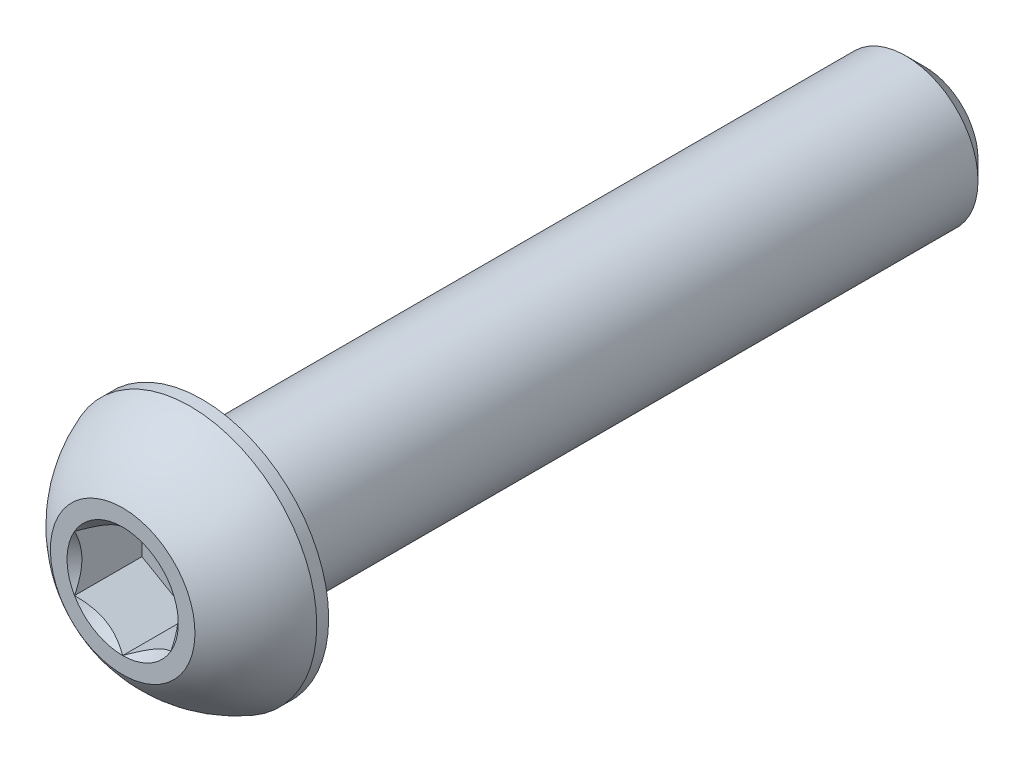
SolidWorks part; units mm, degrees
material "Alloy Steel"
ref_plane "Front Plane" through (0, 0, 0) normal (0, 0, 1) x (1, 0, 0)
ref_plane "Top Plane" through (0, 0, 0) normal (0, 1, 0) x (1, 0, 0)
ref_plane "Right Plane" through (0, 0, 0) normal (1, 0, 0) x (0, 0, -1)
sketch "Sketch1" plane through (0, 0, 0) normal (1, 0, 0) x (0, 0, -1)
  line L0 (-16.65, 0) -> (16.65, 0) construction
  line L1 (-13.35, 5.25) -> (-13.35, -5.25) construction
  line L2 (16.65, 3) -> (16.65, -3) construction
  line L3 (16.5875, 3.1083) -> (17.0875, 2.2422) construction
  line L4 (17.0875, 2.2422) -> (17.5875, 3.1083) construction
  line L5 (17.5875, 3.1083) -> (16.5875, 3.1083) construction
  line L6 (16.65, 3) -> (17.525, 3) construction
  line L7 (17.0875, 3.1083) -> (17.0875, 3) construction
  line L8 (17.0875, 3) -> (17.0875, 2.3505) construction
  line L9 (17.0875, 2.3505) -> (17.0875, 2.2422) construction
  line L10 (17.025, 2.3505) -> (17.15, 2.3505)
  line L11 (16.6188, 3.0541) -> (17.5563, 3.0541)
  line L12 (17.15, 2.3505) -> (17.5563, 3.0541)
  line L13 (17.025, 2.3505) -> (16.6188, 3.0541)
  line L14 (-16.65, 2) -> (-16.65, -2) construction
  line L15 (16.65, 3) -> (-13.35, 3) construction
  point P3 (-13.35, 0)
  point P6 (-13.85, 0)
  point P21 (17.0875, 3.0541)
  point P24 (-13.845, 5.25)
  point P25 (14.15, -3)
  point P26 (-16.65, 3)
  dimension "Head Height" = 3.3
  dimension "Length" = 30
  dimension "Head Dia" = 10.5
  dimension "Thread Dia" = 6
  dimension "Pitch" = 1
  dimension "D2" = 0.125
  dimension "Drive Size" = 4
  dimension "D1" = 2.8
  dimension "D3" = 0.495
  dimension "D4" = 2.5
sketch "Sketch2" plane through (0, 0, 0) normal (1, 0, 0) x (0, 0, -1)
  line L0 (-16.65, 0) -> (16.65, 0)
  line L1 (16.65, 0) -> (16.65, 2.2)
  line L2 (16.65, 3) -> (16.65, -3) construction
  line L3 (16.65, 2.2) -> (15.85, 3)
  line L4 (15.85, 3) -> (-13.35, 3)
  line L5 (-13.35, 5.25) -> (-13.35, -5.25) construction
  line L6 (-13.35, 3) -> (-13.35, 5.25)
  line L7 (-13.35, 5.25) -> (-13.845, 5.25)
  line L8 (16.65, 3) -> (17.525, 3) construction
  line L9 (-16.65, 0) -> (-16.65, 3)
  arc A0 (-16.65, 3) -> (-13.845, 5.25) centre (-11.9387, 0) cw
  dimension "D1" = 0.8
  dimension "D2" = 45
revolve "Revolve1" add sketch "Sketch2" angle 360 about L0
sketch "Sketch3" plane through (0, 0, 16.65) normal (0, 0, 1) x (1, 0, 0)
  line L1 (0, 2.3094) -> (-2, 1.1547)
  line L2 (-2, 1.1547) -> (-2, -1.1547)
  line L3 (-2, -1.1547) -> (0, -2.3094)
  line L4 (0, -2.3094) -> (2, -1.1547)
  line L5 (2, -1.1547) -> (2, 1.1547)
  line L6 (2, 1.1547) -> (0, 2.3094)
  circle A0 centre (0, 0) radius 2 construction
  dimension "D1" = 4
extrude "Cut-Extrude1" cut sketch "Sketch3" against normal up to vertex (2.8 mm away) up to point (0, 0, 13.85)
sketch "Sketch4" plane through (0, 0, 16.65) normal (0, 0, 1) x (1, 0, 0)
  circle A0 centre (0, 0) radius 2.3094
extrude "Cut-Extrude2" cut sketch "Sketch4" against normal blind 10 draft 45
split "Split1" [suppressed] bodies to split 106
sketch "Sketch5" [suppressed] plane through (0, 0, -16.65) normal (0, 0, -1) x (-1, 0, 0)
  circle A0 centre (0, 0) radius 3 construction
  circle A1 centre (0, 0) radius 3
curve "Helix/Spiral1" [suppressed] pitch 1 height 31 turns 31
sketch "Sketch6" [suppressed] plane through (0, 0, 0) normal (1, 0, 0) x (0, 0, -1)
  line L0 (17.025, 2.3505) -> (17.15, 2.3505) construction
  line L1 (17.025, 2.3505) -> (16.6188, 3.0541) construction
  line L2 (16.6188, 3.0541) -> (17.5563, 3.0541) construction
  line L3 (17.15, 2.3505) -> (17.5563, 3.0541) construction
  line L4 (17.025, 2.3505) -> (17.15, 2.3505)
  line L5 (17.025, 2.3505) -> (16.6188, 3.0541)
  line L6 (16.6188, 3.0541) -> (17.5563, 3.0541)
  line L7 (17.15, 2.3505) -> (17.5563, 3.0541)
sweep "Cut-Sweep1" [suppressed] cut profiles "Sketch6" path "Helix/Spiral1"
sketch "Sketch7" [suppressed] plane through (0, 0, 13.35) normal (0, 0, -1) x (-1, 0, 0)
  circle A1 centre (0, 0) radius 3
  circle A2 centre (0, 0) radius 3
  dimension "D1" = 0
extrude "Boss-Extrude1" [suppressed] add sketch "Sketch7" along normal blind 10 draft 30
equation "\"D2@Sketch1\" = \"Pitch@Sketch1\" / 8"
equation "\"D1@Sketch1\"=\"Drive Size@Sketch1\"*.7"
equation "\"D3@Sketch1\"=\"Head Height@Sketch1\"*.15"
equation "\"D1@Sketch2\"=\"Pitch@Sketch1\"*.8"
equation "\"D1@Sketch3\"=\"Drive Size@Sketch1\""
equation "\"D4@Helix/Spiral1\"=\"Pitch@Sketch1\""
equation "\"D3@Helix/Spiral1\"=\"Length@Sketch1\"+\"Pitch@Sketch1\""
equation "\"D4@Sketch1\"=\"Pitch@Sketch1\"*2.5"
